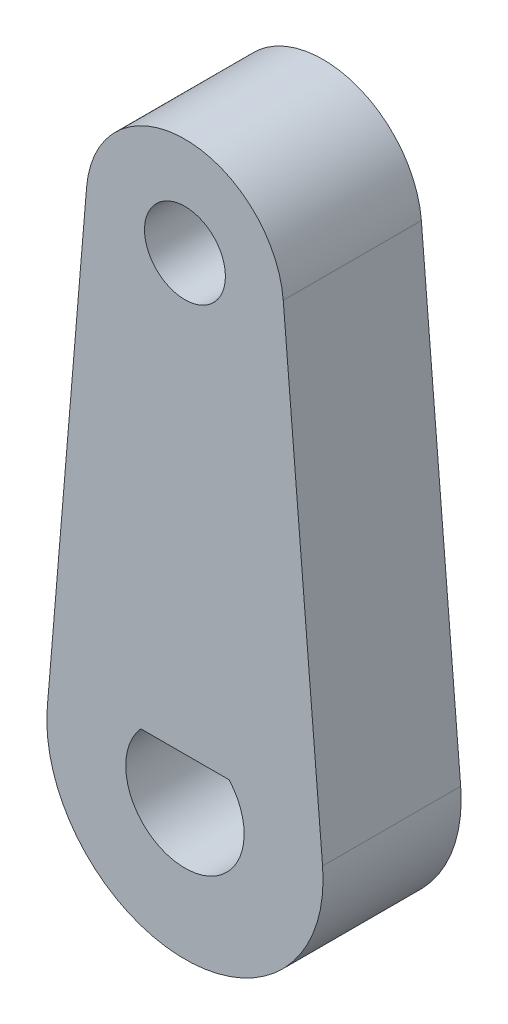
SolidWorks part; units mm, degrees
material "Aluminum 7075-T6 (2)"
ref_plane "Front Plane" through (0, 0, 0) normal (0, 0, 1) x (1, 0, 0)
ref_plane "Top Plane" through (0, 0, 0) normal (0, 1, 0) x (1, 0, 0)
ref_plane "Right Plane" through (0, 0, 0) normal (1, 0, 0) x (0, 0, -1)
sketch "Sketch1" plane through (0, 0, 0) normal (0, 0, 1) x (1, 0, 0)
  line L0 (-2.4913, 12.2083) -> (-3.4878, 0.2917)
  line L1 (2.4913, 12.2083) -> (3.4878, 0.2917)
  arc A0 (-3.4878, 0.2917) -> (3.4878, 0.2917) centre (0, 0) ccw
  arc A1 (2.4913, 12.2083) -> (-2.4913, 12.2083) centre (0, 12) ccw
  dimension "D1" = 7
  dimension "D2" = 5
  dimension "D3" = 12
extrude "Boss-Extrude1" add sketch "Sketch1" along normal blind 3.5
sketch "Sketch2" plane through (0, 0, 3.5) normal (0, 0, 1) x (1, 0, 0)
  line L0 (0, 0) -> (5.6436, 0) construction
  line L1 (-1.118, 1) -> (1.118, 1)
  arc A0 (-1.118, 1) -> (1.118, 1) centre (0, 0) ccw
  circle A1 centre (0, 12) radius 1.025
  dimension "D1" = 1
  dimension "D2" = 3
  dimension "D3" = 2.05
extrude "Cut-Extrude1" cut sketch "Sketch2" against normal through all
